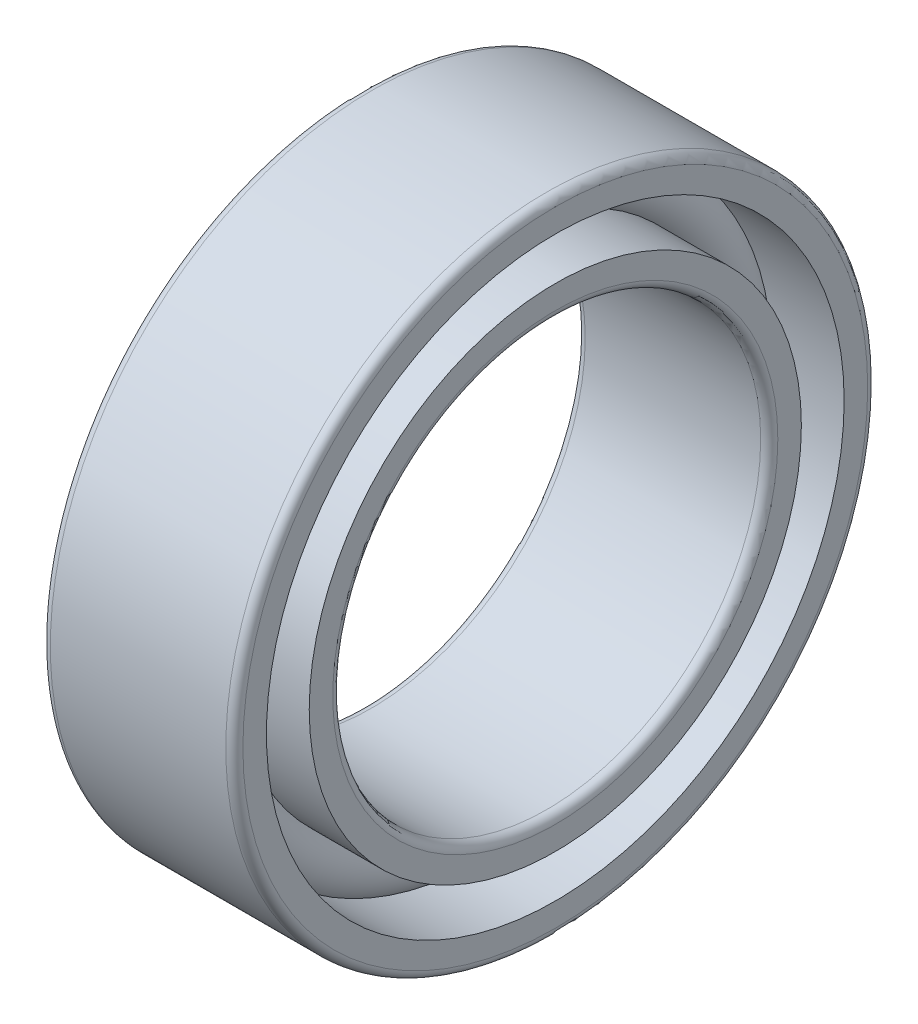
SolidWorks part; units mm, degrees
ref_plane "Plane1" through (0, 0, 0) normal (0, 0, 1) x (1, 0, 0)
ref_plane "Plane2" through (0, 0, 0) normal (0, 1, 0) x (1, 0, 0)
ref_plane "Plane3" through (0, 0, 0) normal (1, 0, 0) x (0, 0, -1)
sketch "Clipboard" plane through (0, 0, 0) normal (0, 0, 1) x (1, 0, 0)
  line L0 (-10, 0) -> (10, 0) construction
  line L1 (0, 0) -> (22.3471, -0.7804)
  line L2 (0, 0) -> (6.2462, 0.2181)
  line L3 (0, 0) -> (22.3471, -0.7804)
  line L4 (0, 0) -> (-22.3573, -0.3902)
sketch "CagSpiSke" plane through (0, 0, 0) normal (0, 0, 1) x (1, 0, 0)
  line L0 (0.075, 6.125) -> (0.075, 6.375)
  line L1 (0.075, 6.375) -> (-0.075, 6.375)
  line L2 (-0.075, 6.375) -> (-0.075, 6.125)
  line L3 (-0.075, 6.125) -> (0.075, 6.125)
  line L4 (-20.6375, 0) -> (20.6375, 0) construction
  line L5 (0, 0) -> (0, 23.7692) construction
revolve "CageSpine" add sketch "CagSpiSke" angle 0.001 about L4 reverse direction yes
ref_axis "Axis1" through (-50, 0, 0) along (1, 0, 0)
sketch "CagBalSke" plane through (0, 0, 0) normal (0, 0, 1) x (1, 0, 0)
  line L0 (-0.825, 6.25) -> (0.825, 6.25)
  line L1 (-1.905, 6.25) -> (1.905, 6.25) construction
  line L2 (-10, 0) -> (10, 0) construction
  line L3 (0, 0) -> (0, 24) construction
  arc A0 (0.825, 6.25) -> (-0.825, 6.25) centre (0, 6.25) cw
revolve "CageBall" [suppressed] add sketch "CagBalSke" angle 360 about L1 reverse direction yes
pattern_circular "CageBalls" [suppressed] count 2 every 180 about axis through (-50, 0, 0) along (1, 0, 0)
sketch "CagTrmODSke" plane through (0, 0, 0) normal (0, 0, 1) x (1, 0, 0)
  line L0 (0.826, 6.375) -> (0.826, 7.076)
  line L1 (0.826, 7.076) -> (-0.826, 7.076)
  line L2 (-0.826, 7.076) -> (-0.826, 6.375)
  line L3 (-0.826, 6.375) -> (0.826, 6.375)
  line L4 (-20.6375, 0) -> (20.6375, 0) construction
  line L5 (0, 0) -> (0, 25) construction
revolve "CageTrimOD" [suppressed] cut sketch "CagTrmODSke" angle 360 about L4 reverse direction yes
sketch "CagTrmIDSke" plane through (0, 0, 0) normal (0, 0, 1) x (1, 0, 0)
  line L0 (0.826, 5.426) -> (0.826, 6.125)
  line L1 (0.826, 6.125) -> (-0.826, 6.125)
  line L2 (-0.826, 6.125) -> (-0.826, 5.426)
  line L3 (-0.826, 5.426) -> (0.826, 5.426)
  line L4 (-20.6375, 0) -> (20.6375, 0) construction
  line L5 (0, 0) -> (0, 25) construction
revolve "CageTrimID" [suppressed] cut sketch "CagTrmIDSke" angle 360 about L4 reverse direction yes
sketch "BalSimSke" plane through (0, 0, 0) normal (0, 0, 1) x (1, 0, 0)
  line L0 (-10, 0) -> (10, 0) construction
  line L1 (-10, 6.25) -> (10, 6.25) construction
  line L2 (0, 0) -> (0, 23) construction
  circle A0 centre (0, 6.25) radius 0.75
revolve "BallsSimplified" add sketch "BalSimSke" angle 360 about L0
sketch "BalDetSke" plane through (0, 0, 0) normal (0, 0, 1) x (1, 0, 0)
  line L0 (-0.75, 6.25) -> (0.75, 6.25)
  line L1 (-1.905, 6.25) -> (1.905, 6.25) construction
  line L2 (0, 0) -> (0, 25) construction
  arc A0 (0.75, 6.25) -> (-0.75, 6.25) centre (0, 6.25) cw
revolve "BallDetailed" [suppressed] add sketch "BalDetSke" angle 360 about L1 reverse direction yes
sketch "InnRacSke" plane through (0, 0, 0) normal (0, 0, 1) x (1, 0, 0)
  line L0 (-0.525, 5.75) -> (-2.25, 5.75)
  line L1 (-2.25, 5.75) -> (-2.25, 5.2)
  line L2 (-2.05, 5) -> (2.05, 5)
  line L3 (2.25, 5.2) -> (2.25, 5.75)
  line L4 (2.25, 5.75) -> (0.525, 5.75)
  line L5 (-20.6375, 0) -> (20.6375, 0) construction
  line L6 (0, 0) -> (0, 30) construction
  arc A0 (-2.25, 5.2) -> (-2.05, 5) centre (-2.05, 5.2) ccw
  arc A1 (2.05, 5) -> (2.25, 5.2) centre (2.05, 5.2) ccw
  arc A2 (0.525, 5.75) -> (-0.525, 5.75) centre (0, 6.25) cw
  dimension "Fillet_radius" = 0.2
  dimension "Width" = 4.5
revolve "InnerRace" add sketch "InnRacSke" angle 360 about L5 reverse direction yes
sketch "OutRacSke" plane through (0, 0, 0) normal (0, 0, 1) x (1, 0, 0)
  line L0 (-0.525, 6.75) -> (-2.25, 6.75)
  line L1 (-2.25, 6.75) -> (-2.25, 7.3)
  line L2 (-2.05, 7.5) -> (2.05, 7.5)
  line L3 (2.25, 7.3) -> (2.25, 6.75)
  line L4 (2.25, 6.75) -> (0.525, 6.75)
  line L5 (-20.6375, 0) -> (20.6375, 0) construction
  line L6 (0, 0) -> (0, 30) construction
  arc A0 (-2.25, 7.3) -> (-2.05, 7.5) centre (-2.05, 7.3) cw
  arc A1 (2.05, 7.5) -> (2.25, 7.3) centre (2.05, 7.3) cw
  arc A2 (0.525, 6.75) -> (-0.525, 6.75) centre (0, 6.25) ccw
  dimension "Fillet_radius" = 0.2
  dimension "Width" = 4.5
revolve "OuterRace" add sketch "OutRacSke" angle 360 about L5 reverse direction yes
pattern_circular "BallsDetailed" [suppressed] count 2 every 180 about axis through (-50, 0, 0) along (1, 0, 0)
equation "\"BallCLRad@Clipboard\" = ( \"OD@OutRacSke\" + \"ID@InnRacSke\" ) / 4"
equation "\"BallCLRad@BalSimSke\" = \"BallCLRad@Clipboard\""
equation "\"BallCLRad@BalDetSke\" = \"BallCLRad@Clipboard\""
equation "\"BallCLRad@InnRacSke\" = \"BallCLRad@Clipboard\""
equation "\"BallCLRad@OutRacSke\" = \"BallCLRad@Clipboard\""
equation "\"Ball_diameter@InnRacSke\" = \"Ball_diameter@BalDetSke\" - 0.05"
equation "\"Ball_diameter@OutRacSke\" = \"Ball_diameter@BalDetSke\" - 0.05"
equation "\"Ball_diameter@BalSimSke\" = \"Ball_diameter@BalDetSke\""
equation "\"Width@OutRacSke\" = \"Width@InnRacSke\""
equation "\"Fillet_radius@OutRacSke\" = \"Fillet_radius@InnRacSke\""
equation "\"Max_count@Clipboard\" = int( 3.14159265 / atn(( \"Ball_diameter@BalDetSke\" / 2) / sqr( \"BallCLRad@Clipboard\"  *  \"BallCLRad@Clipboard\" - ( \"Ball_diameter@BalDetSke\" / 2) *  ( \"Ball_diameter@BalDetSke\" / 2))))"
equation "\"Max_count@Clipboard\" = ((sgn( \"Max_count@Clipboard\" - \"Count@Clipboard\" )-1)*( \"Max_count@Clipboard\" - \"Count@Clipboard\" ))/-2+ \"Count@Clipboard\""
equation "\"Count@BallsDetailed\" = int( \"Show_count@Clipboard\" ) "
equation "\"Count@BallsDetailed\" = ((sgn( \"Count@BallsDetailed\" - \"Max_count@Clipboard\" )-1)*( \"Count@BallsDetailed\" - \"Max_count@Clipboard\" ))/-2+ \"Max_count@Clipboard\""
equation "\"Count@BallsDetailed\" = ((sgn( \"Count@BallsDetailed\" - \"Min_count@Clipboard\" )+1)*( \"Count@BallsDetailed\" - \"Min_count@Clipboard\"))/2 +\"Min_count@Clipboard\""
equation "\"Angle@BallsDetailed\" = 360.0 / \"Max_count@Clipboard\""
equation "\"BallCLRad@CagBalSke\" = \"BallCLRad@Clipboard\""
equation "\"Count@CageBalls\" = \"Count@BallsDetailed\""
equation "\"Angle@CageBalls\" = \"Angle@BallsDetailed\""
equation "\"Angle@CageSpine\" =  \"Angle@CageBalls\" * ( \"Count@CageBalls\" -1 + int( \"Count@CageBalls\" / \"Max_count@Clipboard\" ) )  + 0.001 -  int( \"Count@CageBalls\" / \"Max_count@Clipboard\" ) * 0.001"
equation "\"Angle@CageSpine\" =  \"Angle@CageSpine\" * int( \"Min_count@Clipboard\" / 2) + int(1 / \"Min_count@Clipboard\")  * 0.001"
equation "\"CageWallOD@CagBalSke\" =  \"Ball_diameter@BalDetSke\" * 1.1"
equation "\"Thickness@CagSpiSke\" =  \"Ball_diameter@BalDetSke\" * 0.1"
equation "\"OD@CagTrmODSke\" = \"BallCLRad@Clipboard\" * 2 + \"CageWallOD@CagBalSke\" + 0.002"
equation "\"ID@CagTrmODSke\" = \"BallCLRad@Clipboard\" * 2 + \"Ball_diameter@BalDetSke\" / 6"
equation "\"OD@CagTrmIDSke\" = \"BallCLRad@Clipboard\" * 2 - \"Ball_diameter@BalDetSke\" / 6"
equation "\"ID@CagTrmIDSke\" = \"BallCLRad@Clipboard\" * 2 - \"CageWallOD@CagBalSke\" + 0.002"
equation "\"OD@CagSpiSke\" = \"ID@CagTrmODSke\""
equation "\"ID@CagSpiSke\" = \"OD@CagTrmIDSke\""
equation "\"Width@CagTrmODSke\" = \"CageWallOD@CagBalSke\" + 0.002"
equation "\"Width@CagTrmIDSke\" = \"CageWallOD@CagBalSke\" + 0.002"
